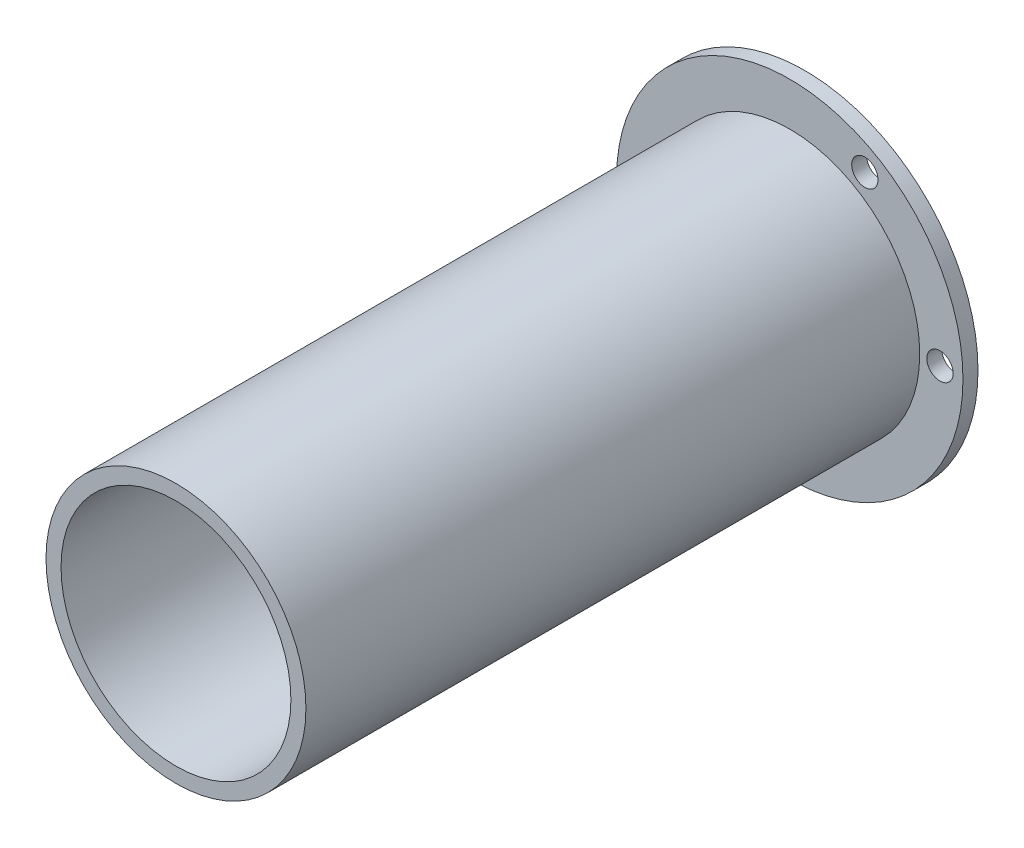
SolidWorks part; units mm, degrees
material "1060 Alloy"
ref_plane "Front Plane" through (0, 0, 0) normal (0, 0, 1) x (1, 0, 0)
ref_plane "Top Plane" through (0, 0, 0) normal (0, 1, 0) x (1, 0, 0)
ref_plane "Right Plane" through (0, 0, 0) normal (1, 0, 0) x (0, 0, -1)
sketch "Sketch1" plane through (0, 0, 0) normal (0, 0, 1) x (1, 0, 0)
  circle A0 centre (0, 0) radius 7.65
  circle A1 centre (0, 0) radius 8.65
  dimension "D1" = 15.3
  dimension "D2" = 17.3
extrude "Boss-Extrude1" add sketch "Sketch1" along normal blind 40.85
sketch "Sketch2" plane through (0, 0, 0) normal (0, 0, -1) x (-1, 0, 0)
  circle A0 centre (0, 0) radius 11.53
  circle A2 centre (0, 0) radius 7.65
  dimension "D1" = 23.06
extrude "Boss-Extrude2" add sketch "Sketch2" along normal blind 1
hole_wizard "Ø2.0mm Dowel Hole1" positions "Sketch10" profile "Sketch11" hole size "Ø2.0" standard "ISO"
sketch "Sketch10" plane through (0, 0, 0) normal (0, 0, 1) x (1, 0, 0)
  point P0 (-10, 0)
  point P7 (0, 0)
  dimension "D1" = 10
sketch "Sketch11" plane through (-10, 0, 0) normal (1, 0, 0) x (0, -1, 0)
  line L0 (0, 0) -> (0, 5.5258)
  line L1 (0, 5.5258) -> (0.875, 5)
  line L2 (0.875, 5) -> (0.875, 0)
  line L5 (0.875, 0) -> (0, 0)
  line L10 (0, 5.5258) -> (-0.875, 5) construction
  line L11 (0, -6.35) -> (0, 107.95) construction
  dimension "Hole Dia." = 1.75
  dimension "Hole Depth" = 5
  dimension "Drill Angle" = 118
pattern_circular "CirPattern1" count 6 over 360 about axis through (0, 0, 0) along (0, 0, -1) skipping 1, 4 of "Ø2.0mm Dowel Hole1"
